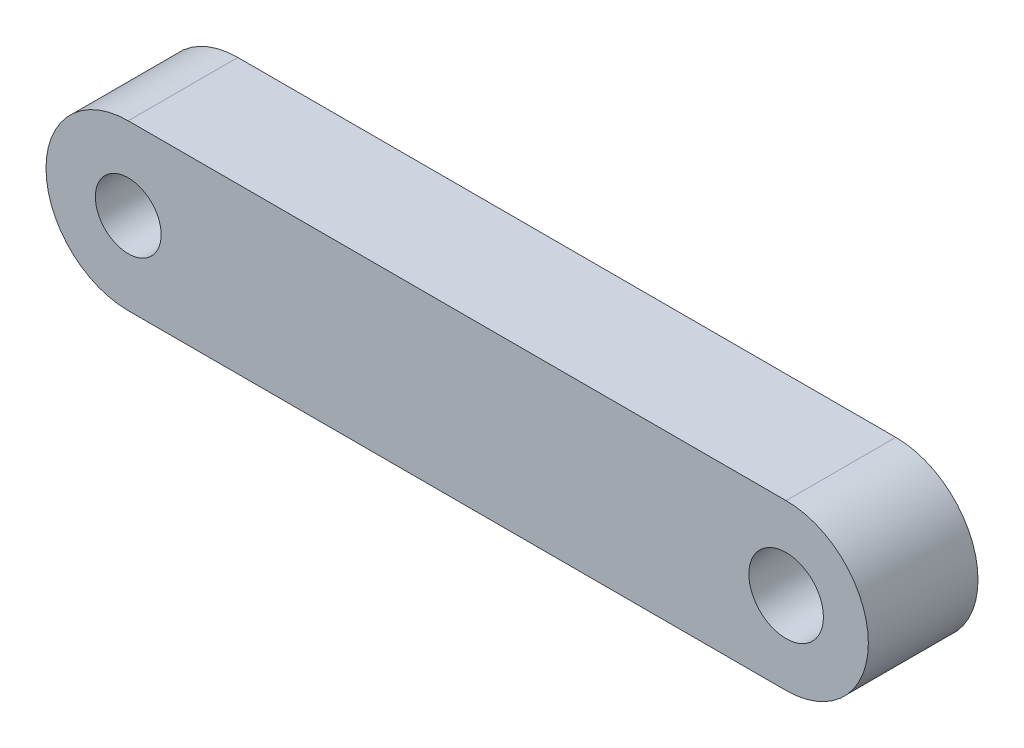
SolidWorks part; units mm, degrees
ref_plane "Front Plane" through (0, 0, 0) normal (0, 0, 1) x (1, 0, 0)
ref_plane "Top Plane" through (0, 0, 0) normal (0, 1, 0) x (1, 0, 0)
ref_plane "Right Plane" through (0, 0, 0) normal (1, 0, 0) x (0, 0, -1)
sketch "Sketch1" plane through (0, 0, 0) normal (0, 0, 1) x (1, 0, 0)
  line L0 (0, 0) -> (38.1, 0) construction
  line L1 (0, 4.7625) -> (38.1, 4.7625)
  line L2 (0, -4.7625) -> (38.1, -4.7625)
  arc A0 (0, 4.7625) -> (0, -4.7625) centre (0, 0) ccw
  arc A1 (38.1, -4.7625) -> (38.1, 4.7625) centre (38.1, 0) ccw
  circle A2 centre (0, 0) radius 1.905
  circle A3 centre (38.1, 0) radius 2.159
  point P3 (19.05, 0)
  dimension "D3" = 3.81
  dimension "D4" = 4.318
  dimension "D1" = 9.525
  dimension "D2" = 38.1
extrude "Boss-Extrude1" add sketch "Sketch1" along normal blind 6.35
